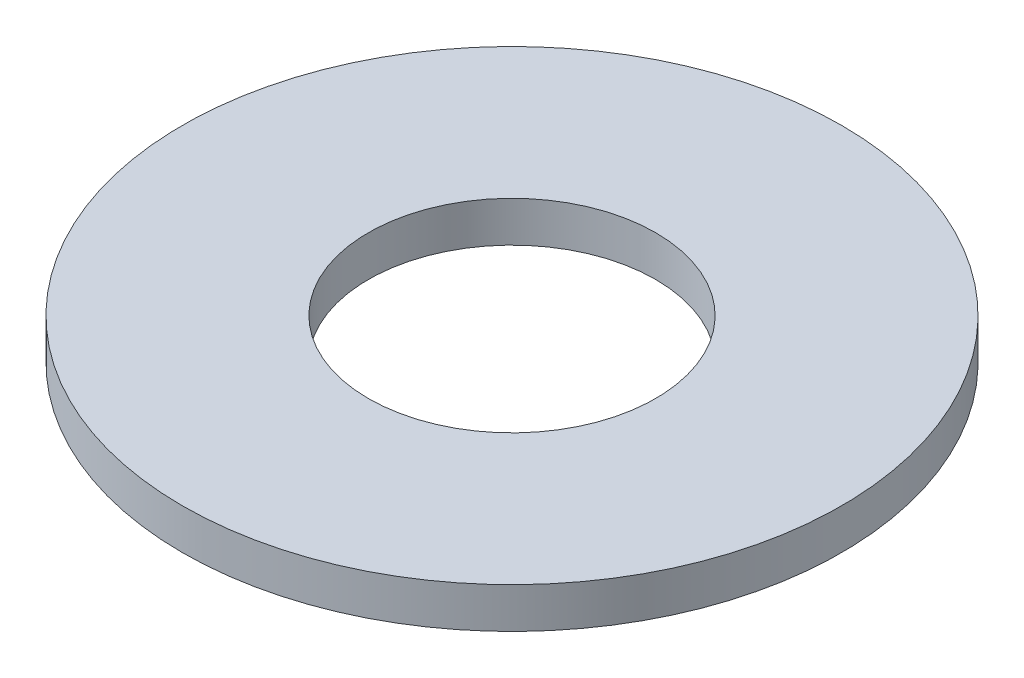
SolidWorks part; units mm, degrees
ref_plane "Front Plane" through (0, 0, 0) normal (0, 0, 1) x (1, 0, 0)
ref_plane "Top Plane" through (0, 0, 0) normal (0, 1, 0) x (1, 0, 0)
ref_plane "Right Plane" through (0, 0, 0) normal (1, 0, 0) x (0, 0, -1)
sketch "Sketch1" plane through (0, 0, 0) normal (0, 1, 0) x (1, 0, 0)
  circle A0 centre (0, 0) radius 97.5
  dimension "FLANGE_OD" = 195
extrude "Boss-Extrude1" add sketch "Sketch1" along normal blind 12
sketch "Sketch2" plane through (0, 0, 0) normal (0, 1, 0) x (1, 0, 0)
  circle A0 centre (0, 0) radius 42.5
  dimension "BORE_D" = 85
extrude "Cut-Extrude1" cut sketch "Sketch2" along normal through all
sketch "Sketch3" plane through (0, 12, 0) normal (0, 1, 0) x (1, 0, 0)
  circle A0 centre (0, 0) radius 30.014 construction
  circle A1 centre (-30.014, 0) radius 5.3219
  dimension "BOLT_D" = 10.6439
  dimension "BOLT_PCD" = 60.028
extrude "Cut-Extrude2" cut sketch "Sketch3" against normal blind 8.2679 rebuild error yes
pattern_circular "CirPattern1" count 3 over 360 rebuild error yes
